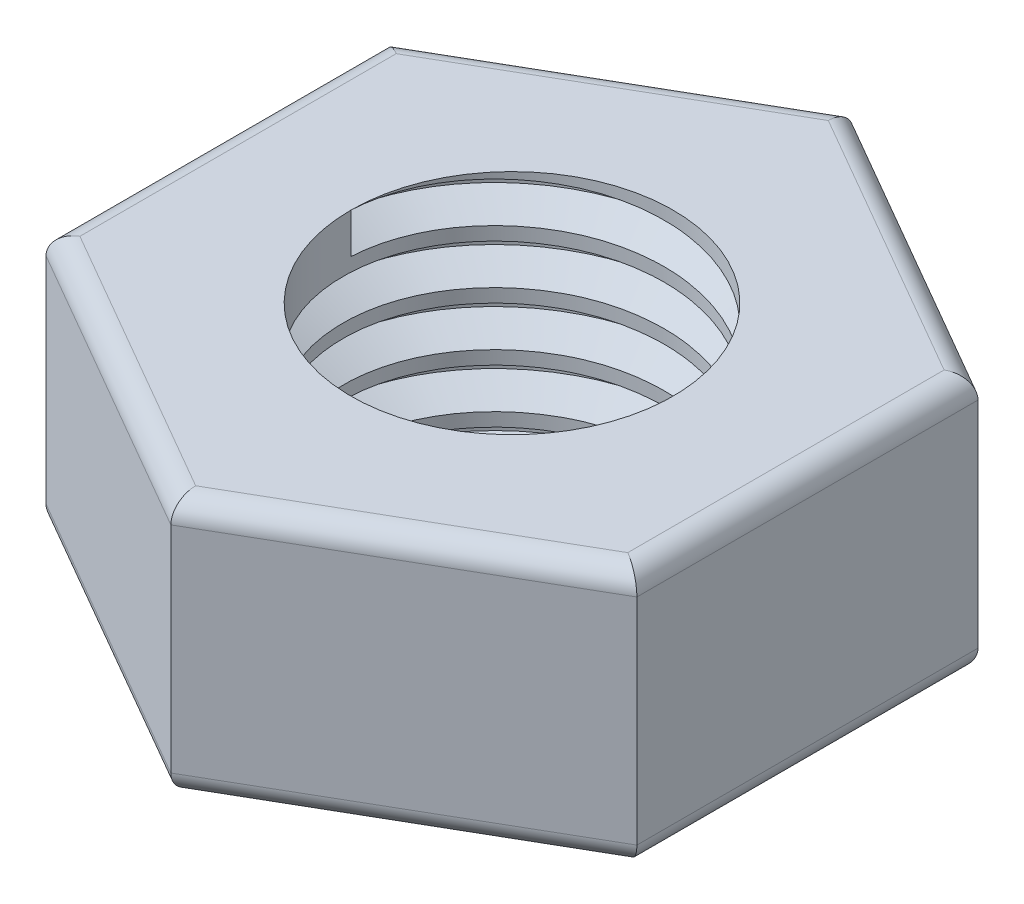
SolidWorks part; units mm, degrees
ref_plane "Front Plane" through (0, 0, 0) normal (0, 0, 1) x (1, 0, 0)
ref_plane "Top Plane" through (0, 0, 0) normal (0, 1, 0) x (1, 0, 0)
ref_plane "Right Plane" through (0, 0, 0) normal (1, 0, 0) x (0, 0, -1)
sketch "Sketch1" plane through (0, 0, 0) normal (0, 1, 0) x (1, 0, 0)
  line L1 (0, 3.1754) -> (-2.75, 1.5877)
  line L2 (-2.75, 1.5877) -> (-2.75, -1.5877)
  line L3 (-2.75, -1.5877) -> (0, -3.1754)
  line L4 (0, -3.1754) -> (2.75, -1.5877)
  line L5 (2.75, -1.5877) -> (2.75, 1.5877)
  line L6 (2.75, 1.5877) -> (0, 3.1754)
  circle A0 centre (0, 0) radius 2.75 construction
  circle A1 centre (0, 0) radius 1.5
  dimension "D1" = 5.5
  dimension "D3" = 3
  dimension "D2" = 1.5877
extrude "Boss-Extrude1" add sketch "Sketch1" along normal blind 2.4
thread "Thread1" pitch 0.5 method cut profile "Thread Profile1" start angle 0, offset 0, length 0, pitch 0.5, diameter 3
ref_plane "Plane1" through (-1.5, 2.4, 0) normal (0, 0, 1) x (-1, 0, 0)
sketch "Thread Profile1" plane through (-1.5, 2.4, 0) normal (0, 0, 1) x (-1, 0, 0)
  line L0 (0, 0) -> (0, 0.5) construction
  line L1 (0, 0) -> (0.2706, 0.1562)
  line L2 (0.2706, 0.1562) -> (0.2706, 0.2187)
  line L3 (0.2706, 0.2187) -> (0, 0.375)
  line L4 (0.2706, 0.1875) -> (0, 0.1875) construction
  line L11 (0, 0) -> (0, 0.375)
  point P2 (0, 0)
  dimension "Pitch" = 0.5
  dimension "Profile_Angle" = 60
  dimension "Profile_Land" = 0.0625
  dimension "Profile_Height" = 0.2706
fillet "Fillet1" radius 0.2 12 edges at (-1.375, 0, -2.3816) (1.375, 0, -2.3816) (2.75, 0, 0) (-1.375, 0, 2.3816) (1.375, 0, 2.3816) (-2.75, 0, 0) (-1.375, 2.4, 2.3816) (1.375, 2.4, 2.3816) (2.75, 2.4, 0) (1.375, 2.4, -2.3816) (-2.75, 2.4, 0) (-1.375, 2.4, -2.3816)
